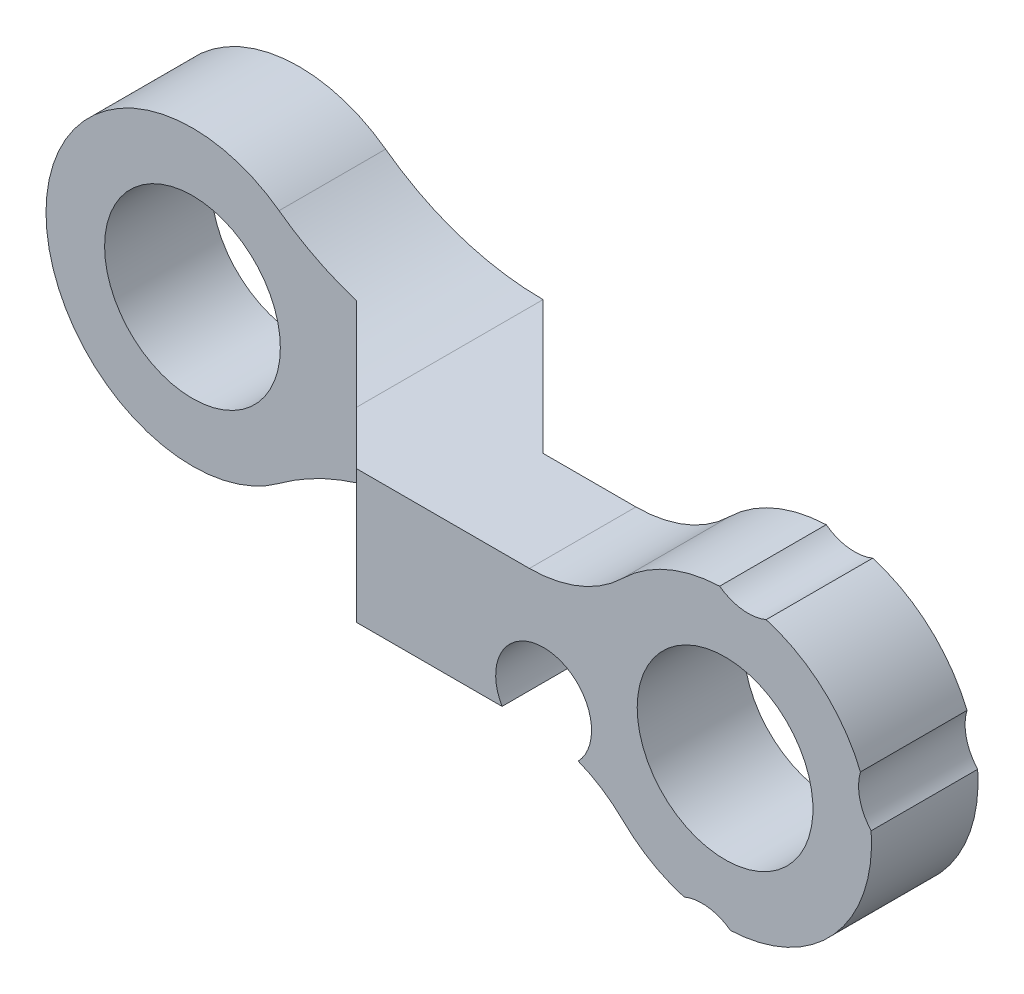
SolidWorks part; units mm, degrees
ref_plane "正面" through (0, 0, 0) normal (0, 0, 1) x (1, 0, 0)
ref_plane "平面" through (0, 0, 0) normal (0, 1, 0) x (1, 0, 0)
ref_plane "右側面" through (0, 0, 0) normal (1, 0, 0) x (0, 0, -1)
sketch "ｽｹｯﾁ1" plane through (0, 0, 0) normal (0, 0, 1) x (1, 0, 0)
  line L1 (2.5, -2.5) -> (-27.5, -2.5)
  line L2 (2.5, -2.5) -> (2.5, 2.5)
  line L3 (2.5, 2.5) -> (-27.5, 2.5)
  line L4 (-27.5, -2.5) -> (-27.5, 2.5)
  circle A1 centre (0, 0) radius 2
  circle A7 centre (-25, 0) radius 5.5
  circle A8 centre (-25, 0) radius 3.3
  point P7 (2.5, 0)
  dimension "D1" = 2.5
  dimension "D3" = 25
  dimension "D5" = 4
  dimension "D6" = 11
  dimension "D9" = 6.6
  dimension "D2" = 2.5
  dimension "D4" = 5
  dimension "D7" = 2.5
  dimension "D8" = 2.5
extrude "ﾎﾞｽ - 押し出し1" add sketch "ｽｹｯﾁ1" along normal blind 4 contours A8 L3 L4 | A8 L4 L1 | A8 L3 A7 L1 L4 | A8 L1 A7 L3 | A7 L1 L2 L3 A1 region at (-9.6965, 0, 0) region at (-30.3486, 0, 0) region at (-20.8897, 0, 0) region at (-27.3876, -2.3876, 0) region at (-27.3876, 2.3876, 0)
fillet "ﾌｨﾚｯﾄ1" radius 10 2 edges at (-20.101, 2.5, 2) (-20.101, -2.5, 2)
fillet "ﾌｨﾚｯﾄ2" radius 2 2 edges at (2.5, 2.5, 2) (2.5, -2.5, 2)
sketch "ｽｹｯﾁ2" plane through (0, 0, 4) normal (0, 0, 1) x (1, 0, 0)
  circle A0 centre (0, 0) radius 13.5
  dimension "D1" = 27
extrude "ﾎﾞｽ - 押し出し2" [suppressed] add sketch "ｽｹｯﾁ2" against normal blind 4
sketch "ｽｹｯﾁ3" [suppressed] plane through (0, 0, 4) normal (0, 0, 1) x (1, 0, 0)
  circle A0 centre (0, 0) radius 12.5
  circle A1 centre (0, 0) radius 12.31
  circle A2 centre (0, 0) radius 11.25
  dimension "D1" = 25
  dimension "D2" = 24.62
  dimension "D3" = 22.5
sketch "ｽｹｯﾁ4" [suppressed] plane through (0, 0, 4) normal (0, 0, 1) x (1, 0, 0)
  line L0 (0, 0) -> (12.31, 0) construction
  circle A1 centre (0, 0) radius 12.31 construction
  spline S0 degree 4 poles (12.31, 0) (12.3485, 0.0017) (12.4561, 0.0115) (12.6589, 0.0505) (12.9814, 0.1425) (13.3857, 0.3027) (13.8844, 0.5544) (14.4379, 0.9043) (15.0083, 1.3425) (15.5792, 1.8672) (16.1068, 2.4351) (16.592, 3.0395) (17.0579, 3.7061) (17.5786, 4.5682) (18.1139, 5.644) (18.6167, 6.9464) (19.0299, 8.4415) (19.3042, 9.968) (19.4462, 11.5121) (19.4619, 13.0627) (19.3579, 14.6092) (19.1396, 16.1446) (18.8138, 17.659) (18.4648, 18.8709) (18.1526, 19.7847) (17.911, 20.4224) (17.7728, 20.7723) (17.6392, 21.0918) (17.5553, 21.2895) (17.4406, 21.5482) (17.3448, 21.7631) (17.1818, 22.1143) (16.9261, 22.6413) (16.6594, 23.1497) (16.4169, 23.5967) (16.2722, 23.8456) (16.1891, 23.9906) knots 0 0 0 0 0 0.005604 0.015718 0.02996 0.048734 0.068727 0.096889 0.125051 0.153212 0.181374 0.209535 0.237696 0.271429 0.327752 0.384075 0.440398 0.496721 0.553044 0.609367 0.66569 0.722013 0.778336 0.834659 0.84874 0.86282 0.876901 0.890982 0.895509 0.900036 0.909091 0.931818 0.954545 0.977273 1 1 1 1 1 construction
  spline S1 degree 4 poles (12.31, 0) (12.3485, 0.0017) (12.4561, 0.0115) (12.6589, 0.0505) (12.9814, 0.1425) (13.3857, 0.3027) (13.8844, 0.5544) (14.4379, 0.9043) (15.0083, 1.3425) (15.5792, 1.8672) (16.1068, 2.4351) (16.592, 3.0395) (17.0579, 3.7061) (17.5786, 4.5682) (18.1139, 5.644) (18.6167, 6.9464) (19.0299, 8.4415) (19.3042, 9.968) (19.4462, 11.5121) (19.4619, 13.0627) (19.3579, 14.6092) (19.1396, 16.1446) (18.8138, 17.659) (18.4648, 18.8709) (18.1526, 19.7847) (17.911, 20.4224) (17.7728, 20.7723) (17.6392, 21.0918) (17.5553, 21.2895) (17.4406, 21.5482) (17.3981, 21.6435) (17.3642, 21.7184) (17.3406, 21.7699) knots 0 0 0 0 0 0.005604 0.015718 0.02996 0.048734 0.068727 0.096889 0.125051 0.153212 0.181374 0.209535 0.237696 0.271429 0.327752 0.384075 0.440398 0.496721 0.553044 0.609367 0.66569 0.722013 0.778336 0.834659 0.84874 0.86282 0.876901 0.890982 0.895509 0.900036 0.909091 0.909091 0.909091 0.909091 0.909091
sketch "ｽｹｯﾁ7" [suppressed] plane through (0, 0, 4) normal (0, 0, 1) x (1, 0, 0)
  line L0 (12.31, 0) -> (0, 0) construction
  line L1 (0, 0) -> (13.4745, -0.8288) construction
  line L2 (11.2288, -0.6907) -> (13.4745, -0.8288) construction
  line L3 (12.31, 0) -> (11.25, 0)
  line L4 (12.2172, -1.5087) -> (11.1652, -1.3787)
  arc A0 (-13.1624, -3) -> (-13.1624, 3) centre (0, 0) ccw construction
  circle A1 centre (0, 0) radius 12.5 construction
  circle A2 centre (0, 0) radius 11.25 construction
  arc A3 (13.3488, -2.015) -> (13.4951, 0.3638) centre (0, 0) ccw
  arc A4 (12.4764, -0.7674) -> (12.5, 0.0221) centre (0, 0) ccw construction
  arc A5 (11.1652, -1.3787) -> (11.25, 0) centre (0, 0) ccw
  spline S0 degree 4 poles (3.7202, 1999.7927) (4.6456, 54.1956) (7.8751, 1.0188) (10.6455, -0.5236) (12.9814, 0.1425) (13.3857, 0.3027) (13.8844, 0.5544) (14.4379, 0.9043) (15.0083, 1.3425) (15.5792, 1.8672) (16.1068, 2.4351) (16.592, 3.0395) (17.0579, 3.7061) (17.5786, 4.5682) (18.1139, 5.644) (18.6167, 6.9464) (19.0299, 8.4415) (19.3042, 9.968) (19.4462, 11.5121) (19.4619, 13.0627) (19.3579, 14.6092) (19.1396, 16.1446) (18.8138, 17.659) (18.4648, 18.8709) (18.1526, 19.7847) (17.911, 20.4224) (17.7728, 20.7723) (17.6392, 21.0918) (17.5553, 21.2895) (16.7643, 23.0728) (18.9302, 18.1286) (-24.8632, 113.3738) (849.1075, -1796.9384) knots -0.304242 -0.304242 -0.304242 -0.304242 -0.304242 0.005604 0.015718 0.02996 0.048734 0.068727 0.096889 0.125051 0.153212 0.181374 0.209535 0.237696 0.271429 0.327752 0.384075 0.440398 0.496721 0.553044 0.609367 0.66569 0.722013 0.778336 0.834659 0.84874 0.86282 0.876901 0.890982 0.895509 0.900036 1.098806 1.098806 1.098806 1.098806 1.098806 only from (12.31, 0) to (17.3406, 21.7699) construction
  spline S1 degree 4 poles (12.31, 0) (12.3485, 0.0017) (12.4561, 0.0115) (12.6589, 0.0505) (12.9589, 0.1361) (13.214, 0.2348) (13.3998, 0.3182) (13.4951, 0.3638) knots 0 0 0 0 0 0.005604 0.015718 0.02996 0.04533 0.04533 0.04533 0.04533 0.04533
  spline S2 degree 4 poles (12.2172, -1.5087) (12.2552, -1.515) (12.3608, -1.538) (12.5573, -1.6016) (12.8445, -1.7232) (13.0856, -1.8525) (13.2598, -1.958) (13.3488, -2.015) knots 0 0 0 0 0 0.005604 0.015718 0.02996 0.04533 0.04533 0.04533 0.04533 0.04533
  point P165 (0, 0)
  dimension "D1" = 0.79
extrude "ｶｯﾄ - 押し出し2" [suppressed] cut sketch "ｽｹｯﾁ7" against normal blind 4
pattern_circular "円形ﾊﾟﾀｰﾝ18" [suppressed] count 25 over 360 of bodies 107
sketch "ｽｹｯﾁ8" plane through (0, 0, 0) normal (0, 0, -1) x (-1, 0, 0)
  line L1 (15.8348, 2.5) -> (15.8348, -2.5)
  circle A0 centre (25, 0) radius 3.3
  circle A1 centre (25, 0) radius 5.5 construction
  circle A2 centre (25, 0) radius 3.3 construction
  arc A3 (21.7478, -4.4355) -> (21.7478, 4.4355) centre (25, 0) ccw construction
  arc A4 (21.7478, 4.4355) -> (15.8348, 2.5) centre (15.8348, 12.5) cw
  arc A5 (21.7478, -4.4355) -> (15.8348, -2.5) centre (15.8348, -12.5) ccw
  arc A6 (21.7478, -4.4355) -> (15.8348, -2.5) centre (15.8348, -12.5) ccw construction
  arc A7 (15.8348, 2.5) -> (21.7478, 4.4355) centre (15.8348, 12.5) ccw construction
  arc A8 (21.7478, 4.4355) -> (21.7478, -4.4355) centre (25, 0) cw
extrude "ﾎﾞｽ - 押し出し3" add sketch "ｽｹｯﾁ8" along normal blind 5
chamfer "面取り1" distance 5 angle 45 1 edges at (-15.8348, 0, 0)
sketch "ｽｹｯﾁ9" plane through (0, 0, 4) normal (0, 0, 1) x (1, 0, 0)
  line L0 (-18.8348, -2.9606) -> (-18.8348, 2.9606)
  line L1 (0.5, -2.5) -> (-15.8348, -2.5) construction
  circle A0 centre (-25, 0) radius 3.3
  circle A1 centre (-25, 0) radius 5.5 construction
  circle A2 centre (-25, 0) radius 3.3 construction
  arc A3 (-21.7478, 4.4355) -> (-21.7478, -4.4355) centre (-25, 0) ccw construction
  arc A4 (-15.8348, -2.5) -> (-21.7478, -4.4355) centre (-15.8348, -12.5) ccw construction
  arc A5 (-21.7478, -4.4355) -> (-18.8348, -2.9606) centre (-15.8348, -12.5) cw
  arc A6 (-21.7478, 4.4355) -> (-18.8348, 2.9606) centre (-15.8348, 12.5) ccw
  arc A7 (-21.7478, 4.4355) -> (-15.8348, 2.5) centre (-15.8348, 12.5) ccw construction
  arc A8 (-21.7478, -4.4355) -> (-21.7478, 4.4355) centre (-25, 0) cw
  dimension "D1" = 3
extrude "ｶｯﾄ - 押し出し3" cut sketch "ｽｹｯﾁ9" against normal blind 5
chamfer "面取り2" distance 5 angle 45 1 edges at (-18.8348, 0, 4)
sketch "ｽｹｯﾁ10" plane through (0, 0, 0) normal (0, 0, -1) x (-1, 0, 0)
  circle A0 centre (0, 0) radius 5.5
  circle A2 centre (0, 0) radius 3.3
  dimension "D1" = 11
  dimension "D2" = 6.6
extrude "ﾎﾞｽ - 押し出し4" add sketch "ｽｹｯﾁ10" against normal blind 4
sketch "ｽｹｯﾁ11" plane through (0, 0, 0) normal (0, 0, -1) x (-1, 0, 0)
  circle A0 centre (0, 0) radius 3.3
extrude "ｶｯﾄ - 押し出し4" cut sketch "ｽｹｯﾁ11" against normal blind 4
fillet "ﾌｨﾚｯﾄ3" radius 5 2 edges at (-4.899, -2.5, 2) (-4.899, 2.5, 2)
sketch "ｽｹｯﾁ12" plane through (0, 0, 4) normal (0, 0, 1) x (1, 0, 0)
  circle A0 centre (-6.8141, -1.6025) radius 1.8
  circle A1 centre (-0.8631, -6.9466) radius 1.8
  circle A2 centre (6.8141, 1.6025) radius 1.8
  circle A3 centre (0.8631, 6.9466) radius 1.8
  dimension "D1" = 3.6
extrude "ｶｯﾄ - 押し出し5" cut sketch "ｽｹｯﾁ12" against normal blind 10
equation "\"m\"= 1"
equation "\"a\"= 20"
equation "\"z\"= 25"
equation "\"d\"= \"z\" * \"m\""
equation "\"db\"= \"d\" * cos ( \"a\" )"
equation "\"da\"= \"d\" + 2 * \"m\""
equation "\"df\"= \"d\" - 2.5 * \"m\""
equation "\"p\"= PI * \"m\" / 4"
